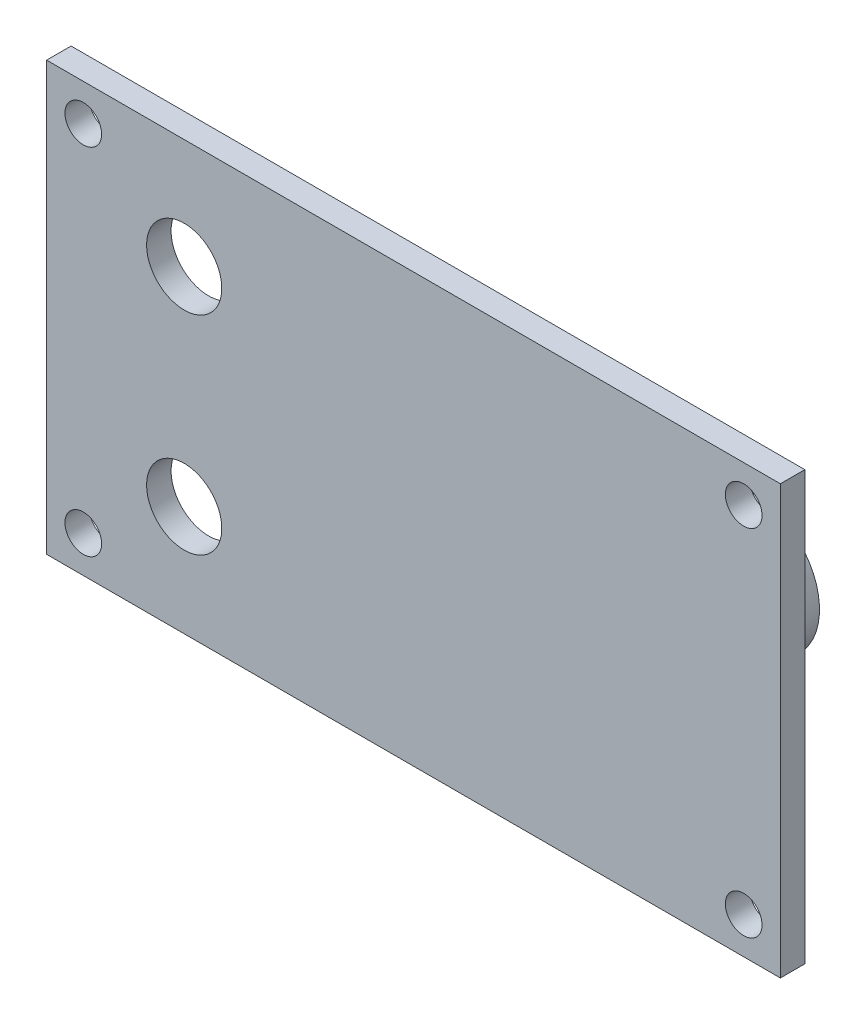
SolidWorks part; units mm, degrees
ref_plane "Front Plane" through (0, 0, 0) normal (0, 0, 1) x (1, 0, 0)
ref_plane "Top Plane" through (0, 0, 0) normal (0, 1, 0) x (1, 0, 0)
ref_plane "Right Plane" through (0, 0, 0) normal (1, 0, 0) x (0, 0, -1)
sketch "Sketch1" plane through (0, 0, 0) normal (0, 0, 1) x (1, 0, 0)
  line L0 (0, 32) -> (60, 32) construction
  line L1 (0, 0) -> (60, 0)
  line L2 (0, 0) -> (0, 35)
  line L3 (0, 35) -> (60, 35)
  line L4 (60, 0) -> (60, 35)
  line L5 (3, 35) -> (3, 0) construction
  line L6 (0, 3) -> (60, 3) construction
  line L7 (57, 35) -> (57, 0) construction
  circle A0 centre (57, 32) radius 1.5
  circle A1 centre (57, 3) radius 1.5
  circle A2 centre (3, 3) radius 1.5
  circle A3 centre (3, 32) radius 1.5
  dimension "D7" = 3
  dimension "D1" = 60
  dimension "D2" = 35
  dimension "D3" = 3
  dimension "D4" = 3
  dimension "D5" = 3
  dimension "D6" = 3
extrude "Boss-Extrude1" add sketch "Sketch1" along normal blind 2
sketch "Sketch2" plane through (0, 0, 0) normal (0, 0, -1) x (-1, 0, 0)
  line L0 (-54.5, 35) -> (-54.5, 0) construction
  line L3 (-18, 35) -> (-18, 0) construction
  line L4 (0, 35) -> (0, 0) construction
  line L5 (-60, 35) -> (0, 35) construction
  line L6 (0, 0) -> (-60, 0) construction
  line L8 (-60, 0) -> (-60, 35) construction
  line L9 (-54.5, 17.5) -> (-18, 17.5) construction
  line L10 (-54.5, 15.5) -> (-18, 15.5) construction
  circle A9 centre (-36.25, 15.5) radius 5.5
  circle A10 centre (-25, 17.5) radius 5.5
  circle A11 centre (-47.5, 17.5) radius 5.5
  dimension "D2" = 2
  dimension "D4" = 11
  dimension "D1" = 5.5
  dimension "D3" = 18
  dimension "D5" = 7
  dimension "D6" = 7
extrude "Boss-Extrude2" add sketch "Sketch2" along normal blind 8.2
sketch "Sketch5" plane through (0, 0, -8.2) normal (0, 0, -1) x (-1, 0, 0)
  circle A0 centre (-47.5, 17.5) radius 3
  circle A1 centre (-36.25, 15.5) radius 3
  circle A2 centre (-25, 17.5) radius 3
  dimension "D1" = 6
extrude "Cut-Extrude2" cut sketch "Sketch5" against normal blind 8.2
sketch "Sketch6" plane through (0, 0, 0) normal (0, 0, -1) x (-1, 0, 0)
  line L0 (-11.25, 35) -> (-11.25, 0) construction
  line L1 (-60, 35) -> (0, 35) construction
  line L2 (0, 0) -> (-60, 0) construction
  line L3 (0, 35) -> (0, 0) construction
  circle A0 centre (-11.25, 26) radius 3.075
  circle A1 centre (-11.25, 9) radius 3.075
  dimension "D4" = 6.15
  dimension "D1" = 11.25
  dimension "D2" = 17
  dimension "D3" = 9
extrude "Cut-Extrude3" cut sketch "Sketch6" against normal blind 8.2
fillet "Fillet4" radius 1 3 edges at (19.5, 17.5, 0) (30.75, 15.5, 0) (42, 17.5, 0)
